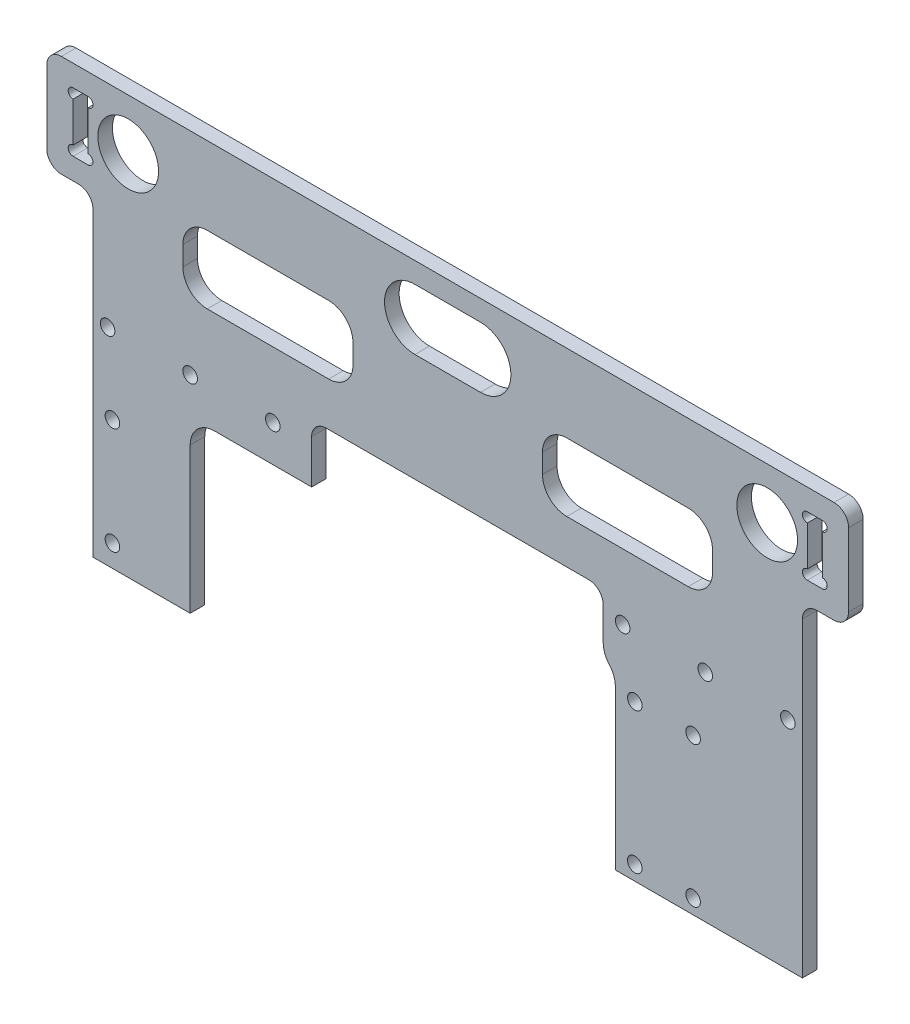
SolidWorks part; units mm, degrees
material "Thornel Mat VMA"
ref_plane "前视基准面" through (0, 0, 0) normal (0, 0, 1) x (1, 0, 0)
ref_plane "上视基准面" through (0, 0, 0) normal (0, 1, 0) x (1, 0, 0)
ref_plane "右视基准面" through (0, 0, 0) normal (1, 0, 0) x (0, 0, -1)
sketch "草图1" plane through (0, 0, 0) normal (0, 0, 1) x (1, 0, 0)
  line L1 (-82.5, 25.5) -> (82.5, 25.5)
  line L2 (-82.5, 25.5) -> (-82.5, -25.5)
  line L3 (-82.5, -25.5) -> (82.5, -25.5)
  line L4 (82.5, 25.5) -> (82.5, -25.5)
  line L5 (-82.5, 25.5) -> (82.5, -25.5) construction
  line L6 (-82.5, -25.5) -> (82.5, 25.5) construction
  point P0 (0, 0)
  dimension "D1" = 51
  dimension "D2" = 165
extrude "凸台-拉伸1" add sketch "草图1" along normal blind 3
sketch "草图2" plane through (0, 0, 3) normal (0, 0, 1) x (1, 0, 0)
  line L0 (-82.5, -18) -> (82.5, -18) construction
  line L1 (-82.5, 25.5) -> (-82.5, -25.5) construction
  line L2 (82.5, -25.5) -> (82.5, 25.5) construction
  line L3 (-82.5, -25.5) -> (82.5, -25.5) construction
  line L4 (0, -18) -> (0, 25.5) construction
  line L5 (82.5, 25.5) -> (-82.5, 25.5) construction
  circle A3 centre (-53, -18) radius 1.5
  circle A4 centre (-36, -18) radius 1.5
  circle A5 centre (36, -18) radius 1.5
  circle A6 centre (53, -18) radius 1.5
  circle A8 centre (-70, -18) radius 1.5
  circle A9 centre (70, -18) radius 1.5
  dimension "D2" = 17
  dimension "D3" = 12.5
  dimension "D4" = 3
  dimension "D5" = 17
  dimension "D1" = 7.5
extrude "切除-拉伸1" cut sketch "草图2" against normal through all
sketch "草图3" plane through (0, 0, 3) normal (0, 0, 1) x (1, 0, 0)
  line L0 (0, 25.5) -> (0, -25.5) construction
  line L1 (82.5, 25.5) -> (-82.5, 25.5) construction
  line L2 (-82.5, -25.5) -> (82.5, -25.5) construction
  line L3 (-65.75, 15) -> (0, 15) construction
  line L4 (-6.75, 15) -> (6.75, 15) construction
  line L5 (-6.75, 21.25) -> (6.75, 21.25)
  line L6 (-6.75, 8.75) -> (6.75, 8.75)
  line L11 (77.1, 8.9) -> (74, 21.1) construction
  line L12 (-77.1, 21.1) -> (-74, 21.1)
  line L13 (-77.1, 21.1) -> (-77.1, 8.9)
  line L14 (-77.1, 8.9) -> (-74, 8.9)
  line L15 (-74, 21.1) -> (-74, 8.9)
  line L16 (-77.1, 21.1) -> (-74, 8.9) construction
  line L17 (-77.1, 8.9) -> (-74, 21.1) construction
  line L18 (77.1, 21.1) -> (74, 8.9) construction
  line L19 (74, 21.1) -> (74, 8.9)
  line L20 (77.1, 8.9) -> (74, 8.9)
  line L21 (77.1, 21.1) -> (77.1, 8.9)
  line L22 (77.1, 21.1) -> (74, 21.1)
  circle A0 centre (-65.75, 15) radius 6.25
  arc A1 (-6.75, 21.25) -> (-6.75, 8.75) centre (-6.75, 15) ccw
  arc A2 (6.75, 8.75) -> (6.75, 21.25) centre (6.75, 15) ccw
  circle A3 centre (65.75, 15) radius 6.25
  point P11 (0, 15)
  point P16 (-75.55, 15)
  point P27 (75.55, 15)
  dimension "D1" = 65.75
  dimension "D2" = 12.5
  dimension "D3" = 40.5
  dimension "D4" = 59
  dimension "D5" = 3.1
  dimension "D6" = 12.2
  dimension "D7" = 74
extrude "切除-拉伸2" cut sketch "草图3" against normal through all
sketch "草图5" plane through (0, 0, 0) normal (0, 0, -1) x (-1, 0, 0)
  line L0 (0, 25.5) -> (0, -25.5) construction
  line L1 (-82.5, -25.5) -> (-73, -25.5)
  line L2 (-82.5, -25.5) -> (-82.5, 4.5)
  line L3 (-82.5, 4.5) -> (-73, 4.5)
  line L4 (-73, -25.5) -> (-73, 4.5)
  line L5 (-82.5, 25.5) -> (82.5, 25.5) construction
  line L6 (82.5, -25.5) -> (-82.5, -25.5) construction
  line L7 (73, -25.5) -> (73, 4.5)
  line L8 (82.5, 4.5) -> (73, 4.5)
  line L9 (82.5, -25.5) -> (82.5, 4.5)
  line L10 (82.5, -25.5) -> (73, -25.5)
  dimension "D1" = 73
  dimension "D2" = 30
extrude "切除-拉伸4" cut sketch "草图5" against normal through all
fillet "圆角1" radius 3 6 edges at (-82.5, 25.5, 1.5) (-82.5, 4.5, 1.5) (-73, 4.5, 1.5) (82.5, 4.5, 1.5) (82.5, 25.5, 1.5) (73, 4.5, 1.5)
sketch "草图6" plane through (0, 0, 0) normal (0, 0, -1) x (-1, 0, 0)
  line L0 (73, 1.5) -> (73, -25.5) construction
  line L3 (53, -25.5) -> (53, -60.5)
  line L4 (-73, -25.5) -> (-34.5, -25.5)
  line L5 (-73, -25.5) -> (-73, -62.5)
  line L6 (-73, -62.5) -> (-34.5, -62.5)
  line L7 (-34.5, -25.5) -> (-34.5, -62.5)
  line L8 (73, -60.5) -> (53, -60.5)
  line L9 (73, -25.5) -> (73, -60.5)
  line L10 (73, -25.5) -> (53, -25.5)
  line L11 (73, -25.5) -> (-73, -25.5) construction
  dimension "D1" = 38.5
  dimension "D2" = 37
  dimension "D3" = 20
  dimension "D4" = 35
extrude "凸台-拉伸2" add sketch "草图6" against normal up to surface (3 mm away) up to face at (0, 5.8745, 3)
sketch "草图4" plane through (0, 0, 3) normal (0, 0, 1) x (1, 0, 0)
  line L0 (-74, 8.9) -> (-74, 21.1) construction
  line L1 (-77.1, 21.1) -> (-77.1, 8.9) construction
  line L2 (-74, 21.1) -> (-77.1, 21.1) construction
  line L3 (-77.1, 8.9) -> (-74, 8.9) construction
  line L4 (0, 25.5) -> (0, -25.5) construction
  line L5 (79.5, 25.5) -> (-79.5, 25.5) construction
  line L7 (-53, -25.5) -> (34.5, -25.5) construction
  circle A0 centre (-74, 20.1) radius 1
  circle A1 centre (-74, 9.9) radius 1
  circle A2 centre (-77.1, 9.9) radius 1
  circle A3 centre (-77.1, 20.1) radius 1
  circle A4 centre (77.1, 20.1) radius 1
  circle A5 centre (77.1, 9.9) radius 1
  circle A6 centre (74, 9.9) radius 1
  circle A7 centre (74, 20.1) radius 1
  dimension "D1" = 2
extrude "切除-拉伸3" cut sketch "草图4" against normal through all
sketch "草图8" plane through (0, 0, 3) normal (0, 0, 1) x (1, 0, 0)
  line L0 (-69, -60.5) -> (-69, -34) construction
  line L1 (-53, -60.5) -> (-73, -60.5) construction
  line L2 (34.5, -62.5) -> (34.5, -25.5) construction
  line L4 (38.5, -30.5) -> (50.5, -30.5) construction
  line L5 (38.5, -30.5) -> (38.5, -59.5) construction
  line L7 (38.5, -59.5) -> (50.5, -59.5) construction
  line L8 (-53, -25.5) -> (-53, -60.5) construction
  line L9 (50.5, -30.5) -> (50.5, -59.5) construction
  line L10 (38.5, -30.5) -> (50.5, -59.5) construction
  line L11 (38.5, -59.5) -> (50.5, -30.5) construction
  line L12 (73, -62.5) -> (34.5, -62.5) construction
  circle A0 centre (-69, -56) radius 1.5
  circle A1 centre (-69, -34) radius 1.5
  circle A4 centre (38.5, -30.5) radius 1.5
  circle A5 centre (38.5, -59.5) radius 1.5
  circle A6 centre (50.5, -59.5) radius 1.5
  circle A7 centre (50.5, -30.5) radius 1.5
  point P9 (44.5, -45)
  dimension "D2" = 4.5
  dimension "D4" = 3
  dimension "D8" = 3
  dimension "D9" = 3
  dimension "D1" = 16
  dimension "D3" = 22
  dimension "D5" = 12
  dimension "D6" = 29
  dimension "D7" = 4
extrude "切除-拉伸6" cut sketch "草图8" against normal through all
fillet "圆角2" radius 5 1 edges at (-53, -25.5, 1.5)
sketch "草图10" plane through (0, 0, 3) normal (0, 0, 1) x (1, 0, 0)
  line L0 (-37, 25.5) -> (-37, -25.5) construction
  line L1 (79.5, 25.5) -> (-79.5, 25.5) construction
  line L2 (-48, -25.5) -> (34.5, -25.5) construction
  line L3 (0, 25.5) -> (0, -25.5) construction
  line L4 (54.5, -4.5) -> (19.5, -4.5)
  line L5 (-54.5, 9.5) -> (-19.5, 9.5)
  line L6 (-54.5, 9.5) -> (-54.5, -4.5)
  line L7 (-54.5, -4.5) -> (-19.5, -4.5)
  line L8 (-19.5, 9.5) -> (-19.5, -4.5)
  line L9 (-54.5, 9.5) -> (-19.5, -4.5) construction
  line L10 (-54.5, -4.5) -> (-19.5, 9.5) construction
  line L11 (19.5, 9.5) -> (19.5, -4.5)
  line L12 (54.5, 9.5) -> (19.5, 9.5)
  line L13 (54.5, 9.5) -> (54.5, -4.5)
  point P9 (-37, 2.5)
  dimension "D1" = 37
  dimension "D2" = 21
  dimension "D3" = 14
  dimension "D4" = 35
extrude "切除-拉伸8" cut sketch "草图10" against normal through all
fillet "圆角3" radius 5 8 edges at (19.5, 9.5, 1.5) (54.5, 9.5, 1.5) (54.5, -4.5, 1.5) (19.5, -4.5, 1.5) (-54.5, -4.5, 1.5) (-19.5, -4.5, 1.5) (-19.5, 9.5, 1.5) (-54.5, 9.5, 1.5)
sketch "草图11" plane through (0, 0, 3) normal (0, 0, 1) x (1, 0, 0)
  line L0 (-48, -25.5) -> (34.5, -25.5) construction
  line L1 (-28, -25.5) -> (32, -25.5)
  line L2 (-28, -25.5) -> (-28, -13.5)
  line L3 (-28, -13.5) -> (32, -13.5)
  line L4 (32, -25.5) -> (32, -13.5)
  line L5 (73, -62.5) -> (73, 1.5) construction
  line L6 (-73, 1.5) -> (-73, -60.5) construction
  dimension "D1" = 12
  dimension "D2" = 41
  dimension "D3" = 45
extrude "切除-拉伸9" cut sketch "草图11" against normal through all
fillet "圆角4" radius 3 2 edges at (32, -13.5, 1.5) (-28, -13.5, 1.5)
fillet "圆角5" radius 5 1 edges at (34.5, -25.5, 1.5)
fillet "圆角6" radius 5 1 edges at (32, -25.5, 1.5)
